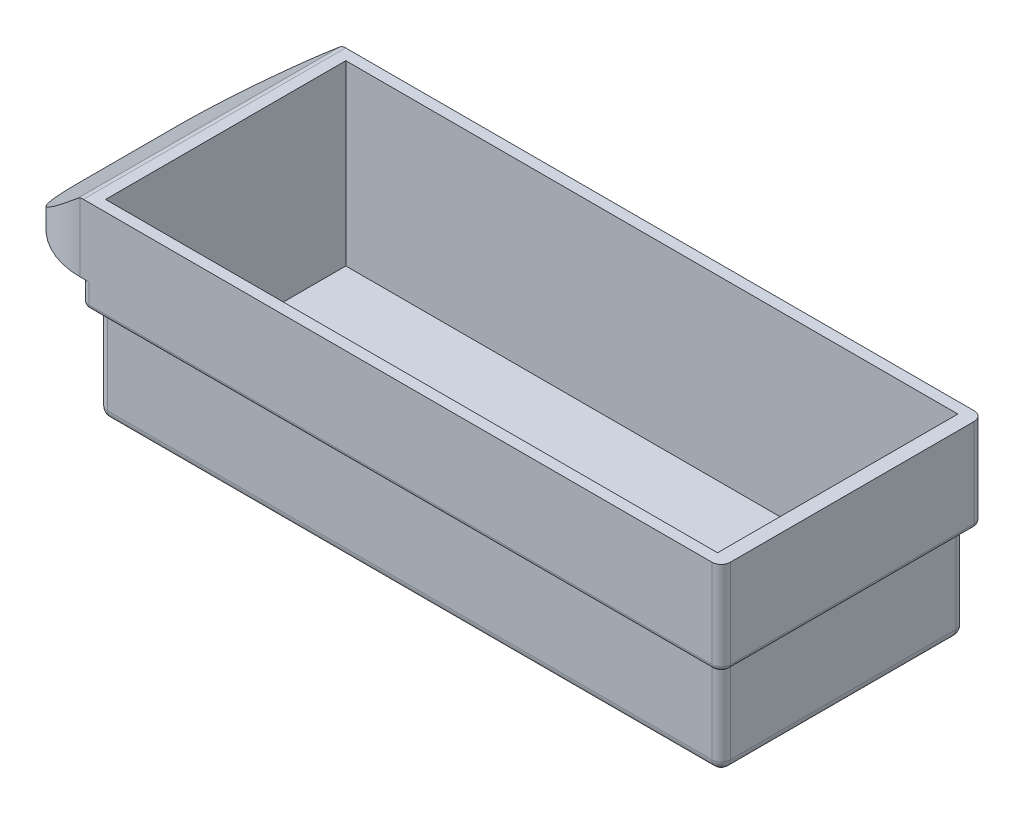
SolidWorks part; units mm, degrees
ref_plane "Front Plane" through (0, 0, 0) normal (0, 0, 1) x (1, 0, 0)
ref_plane "Top Plane" through (0, 0, 0) normal (0, 1, 0) x (1, 0, 0)
ref_plane "Right Plane" through (0, 0, 0) normal (1, 0, 0) x (0, 0, -1)
sketch "Sketch1" plane through (0, 0, 0) normal (0, 1, 0) x (1, 0, 0)
  line L1 (-69.85, -28.575) -> (69.85, -28.575)
  line L2 (-69.85, -28.575) -> (-69.85, 28.575)
  line L3 (-69.85, 28.575) -> (69.85, 28.575)
  line L4 (69.85, -28.575) -> (69.85, 28.575)
  line L5 (-69.85, -28.575) -> (69.85, 28.575) construction
  line L6 (-69.85, 28.575) -> (69.85, -28.575) construction
  point P0 (0, 0)
  dimension "D1" = 139.7
  dimension "D2" = 57.15
extrude "Boss-Extrude1" add sketch "Sketch1" along normal blind 20.32
sketch "Sketch2" plane through (0, 0, 0) normal (0, -1, 0) x (1, 0, 0)
  line L16 (67.85, -26.575) -> (67.85, 26.575)
  line L17 (67.85, 26.575) -> (-67.85, 26.575)
  line L18 (-67.85, 26.575) -> (-67.85, -26.575)
  line L19 (-67.85, -26.575) -> (67.85, -26.575)
  line L20 (67.85, -26.575) -> (67.85, 26.575)
  line L21 (67.85, 26.575) -> (-67.85, 26.575)
  line L22 (-67.85, 26.575) -> (-67.85, -26.575)
  line L23 (-67.85, -26.575) -> (67.85, -26.575)
  dimension "D1" = 2
extrude "Boss-Extrude2" add sketch "Sketch2" along normal blind 20.955
sketch "Sketch3" plane through (0, 0, 28.575) normal (0, 0, 1) x (1, 0, 0)
  line L0 (-69.85, 20.32) -> (-87.7263, 5.32)
  line L1 (-87.7263, 5.32) -> (-69.85, 5.32)
  line L2 (-69.85, 20.32) -> (-69.85, 0) construction
  line L3 (-69.85, 5.32) -> (-69.85, 20.32)
  dimension "D1" = 15
  dimension "D2" = 40
extrude "Boss-Extrude3" add sketch "Sketch3" against normal through all
sketch "Sketch4" plane through (0, 5.32, 0) normal (0, -1, 0) x (1, 0, 0)
  line L0 (-87.7263, -28.575) -> (-87.7263, 28.575) construction
  line L1 (-69.85, -28.575) -> (-87.7263, -28.575)
  line L2 (-87.7263, -28.575) -> (-87.7263, -10.6987)
  line L3 (-87.7263, 10.6987) -> (-87.7263, 28.575)
  line L4 (-87.7263, 28.575) -> (-69.85, 28.575)
  arc A0 (-69.85, 28.575) -> (-87.7263, 10.6987) centre (-69.85, 10.6987) ccw
  arc A1 (-69.85, -28.575) -> (-87.7263, -10.6987) centre (-69.85, -10.6987) cw
extrude "Cut-Extrude1" cut sketch "Sketch4" against normal through all
fillet "Fillet1" radius 2 13 edges at (-69.85, 20.32, 0) (-69.85, 2.66, -28.575) (-67.85, -10.4775, -26.575) (69.85, 10.16, -28.575) (67.85, -10.4775, -26.575) (69.85, 10.16, 28.575) (67.85, -10.4775, 26.575) (-67.85, -10.4775, 26.575) (-69.85, 2.66, 28.575) (-67.85, -20.955, 0) (0, -20.955, 26.575) (67.85, -20.955, 0) (0, -20.955, -26.575)
fillet "Fillet2" radius 1 16 edges at (-69.2642, 0, 27.9892) (-69.85, 0, 0) (-69.2642, 0, -27.9892) (0, 0, -28.575) (69.2642, 0, -27.9892) (69.85, 0, 0) (69.2642, 0, 27.9892) (67.2642, 0, 25.9892) (67.85, 0, 0) (67.2642, 0, -25.9892) (0, 0, -26.575) (-67.2642, 0, -25.9892) (-67.85, 0, 0) (-67.2642, 0, 25.9892) (0, 0, 28.575) (0, 0, 26.575)
sketch "Sketch5" plane through (0, 20.32, 0) normal (0, 1, 0) x (1, 0, 0)
  line L1 (-66.675, -26.175) -> (66.675, -26.175)
  line L2 (-66.675, -26.175) -> (-66.675, 26.175)
  line L3 (-66.675, 26.175) -> (66.675, 26.175)
  line L4 (66.675, -26.175) -> (66.675, 26.175)
  line L5 (-66.675, -26.175) -> (66.675, 26.175) construction
  line L6 (-66.675, 26.175) -> (66.675, -26.175) construction
  point P0 (0, 0)
  dimension "D1" = 133.35
  dimension "D2" = 52.35
extrude "Cut-Extrude2" cut sketch "Sketch5" against normal blind 38.735
